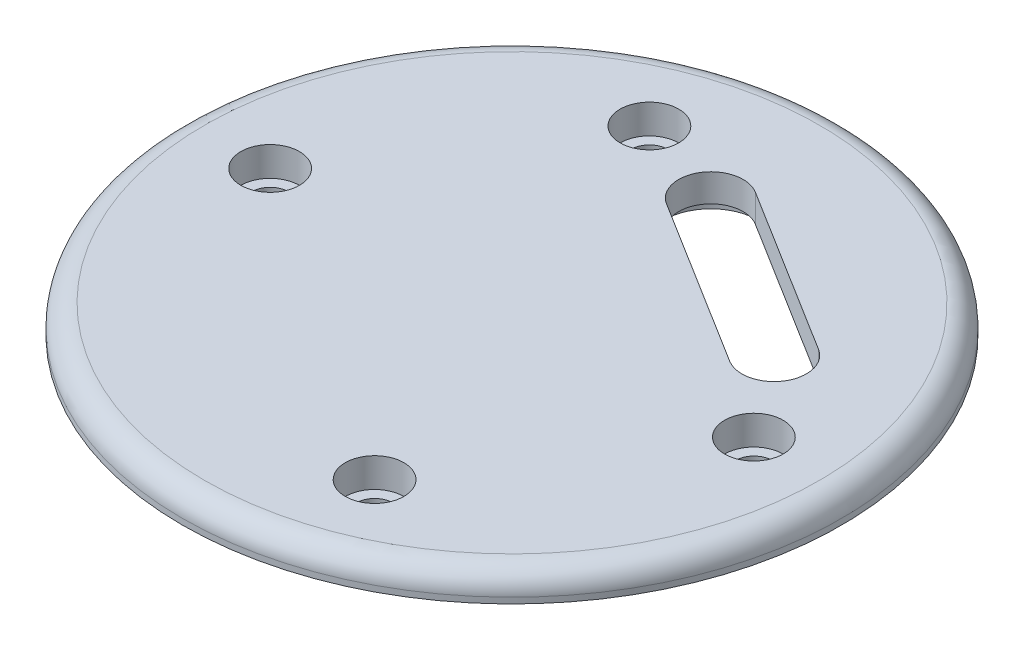
SolidWorks part; units mm, degrees
ref_plane "Front Plane" through (0, 0, 0) normal (0, 0, 1) x (1, 0, 0)
ref_plane "Top Plane" through (0, 0, 0) normal (0, 1, 0) x (1, 0, 0)
ref_plane "Right Plane" through (0, 0, 0) normal (1, 0, 0) x (0, 0, -1)
sketch "Sketch1" plane through (0, 0, 0) normal (0, 1, 0) x (1, 0, 0)
  circle A0 centre (0, 0) radius 22.5
  dimension "D1" = 45
extrude "Boss-Extrude1" add sketch "Sketch1" along normal blind 1.9
sketch "Sketch2" plane through (0, 0, 0) normal (0, -1, 0) x (1, 0, 0)
  circle A0 centre (16.1994, -0.3127) radius 1.25
  circle A1 centre (-5.762, -15.1432) radius 1.25
  circle A2 centre (-16.1994, 0.3127) radius 1.25
  circle A4 centre (5.762, 15.1432) radius 1.25
extrude "Cut-Extrude1" cut sketch "Sketch2" against normal through all
sketch "Sketch3" plane through (0, 1.9, 0) normal (0, 1, 0) x (1, 0, 0)
  line L3 (-0.4607, 11.287) -> (10.9956, 4.1452) construction
  line L6 (13.1116, 7.5397) -> (1.6554, 14.6814) construction
  line L7 (-0.4607, 11.287) -> (10.9956, 4.1452)
  line L8 (13.1116, 7.5397) -> (1.6554, 14.6814)
  line L9 (-0.5665, 11.1173) -> (10.8898, 3.9755)
  line L10 (13.2174, 7.7094) -> (1.7612, 14.8511)
  arc A6 (10.9956, 4.1452) -> (13.1116, 7.5397) centre (12.0536, 5.8425) ccw construction
  arc A7 (1.6554, 14.6814) -> (-0.4607, 11.287) centre (0.5974, 12.9842) ccw construction
  arc A8 (10.9956, 4.1452) -> (13.1116, 7.5397) centre (12.0536, 5.8425) ccw
  arc A9 (1.6554, 14.6814) -> (-0.4607, 11.287) centre (0.5974, 12.9842) ccw
  arc A10 (1.7612, 14.8511) -> (-0.5665, 11.1173) centre (0.5974, 12.9842) ccw
  arc A11 (10.8898, 3.9755) -> (13.2174, 7.7094) centre (12.0536, 5.8425) ccw
  dimension "D1" = 0.2
extrude "Cut-Extrude2" cut sketch "Sketch3" against normal blind 3 contours L8 A9 L7 A8 | L9 A11 L10 A10 A9 L8 A8 L7 region at (6.3255, 1.9, -9.4133) region at (-1.1032, 1.9, -14.0443)
sketch "Sketch5" plane through (0, 0, 0) normal (0, -1, 0) x (1, 0, 0)
  line L0 (-17.0875, 10.8507) -> (-17.5366, 13.064) construction
  line L1 (-17.5366, 13.064) -> (-5.5772, 21.1402) construction
  line L2 (-5.5772, 21.1402) -> (-3.6638, 19.8944) construction
  line L3 (-17.0875, 10.8507) -> (-17.5366, 13.064)
  line L4 (-17.5366, 13.064) -> (-5.5772, 21.1402)
  line L5 (-5.5772, 21.1402) -> (-3.6638, 19.8944)
  line L6 (-17.314, 12.973) -> (-5.5752, 20.9002)
  line L7 (-5.5752, 20.9002) -> (-3.7729, 19.7268)
  line L8 (-16.8915, 10.8904) -> (-17.314, 12.973)
  line L15 (13.2174, -7.7094) -> (1.7612, -14.8511) construction
  line L16 (-0.5665, -11.1173) -> (10.8898, -3.9755) construction
  line L17 (13.2174, -7.7094) -> (1.7612, -14.8511)
  line L18 (-0.5665, -11.1173) -> (10.8898, -3.9755)
  line L19 (-1.0955, -10.2687) -> (10.3607, -3.1269)
  line L20 (13.7465, -8.558) -> (2.2902, -15.6998)
  line L27 (24.6137, -13.9677) -> (22.4818, 0.9048)
  line L28 (24.6137, -13.9677) -> (22.4818, 0.9048)
  line L29 (22.1304, -15.5901) -> (24.6137, -13.9677)
  line L30 (22.1304, -15.5901) -> (24.6137, -13.9677)
  line L31 (19.3957, -11.4042) -> (22.1304, -15.5901)
  line L32 (19.3957, -11.4042) -> (22.1304, -15.5901)
  line L33 (5.387, -26.529) -> (2.6523, -22.3431)
  line L34 (5.387, -26.529) -> (2.6523, -22.3431)
  line L35 (2.9457, -28.124) -> (5.387, -26.529)
  line L36 (2.9457, -28.124) -> (5.387, -26.529)
  line L37 (-6.9155, -21.4109) -> (2.9457, -28.124)
  line L38 (-6.9155, -21.4109) -> (2.9457, -28.124)
  line L39 (-24.5718, 13.9951) -> (-22.3854, 2.2678)
  line L40 (-24.5718, 13.9951) -> (-22.3854, 2.2678)
  line L41 (-22.1304, 15.5901) -> (-24.5718, 13.9951)
  line L42 (-22.1304, 15.5901) -> (-24.5718, 13.9951)
  line L43 (-19.3957, 11.4042) -> (-22.1304, 15.5901)
  line L44 (-19.3957, 11.4042) -> (-22.1304, 15.5901)
  line L45 (-5.387, 26.529) -> (-2.6523, 22.3431)
  line L46 (-5.387, 26.529) -> (-2.6523, 22.3431)
  line L47 (-2.9037, 28.1514) -> (-5.387, 26.529)
  line L48 (-2.9037, 28.1514) -> (-5.387, 26.529)
  line L49 (9.8596, 20.2247) -> (-2.9037, 28.1514)
  line L50 (9.8596, 20.2247) -> (-2.9037, 28.1514)
  arc A0 (-17.3572, 8.8869) -> (-17.0875, 10.8507) centre (-20.0276, 10.2541) ccw construction
  arc A1 (2.6523, -22.3431) -> (19.3957, -11.4042) centre (0, 0) ccw
  arc A3 (-17.3572, 8.8869) -> (-1.7567, 19.4207) centre (0, 0) ccw construction
  arc A4 (-3.6638, 19.8944) -> (-1.7567, 19.4207) centre (-2.0269, 22.4085) ccw construction
  arc A5 (-17.3572, 8.8869) -> (-17.0875, 10.8507) centre (-20.0276, 10.2541) ccw
  arc A6 (-17.3572, 8.8869) -> (-1.7567, 19.4207) centre (0, 0) ccw
  arc A7 (-3.6638, 19.8944) -> (-1.7567, 19.4207) centre (-2.0269, 22.4085) ccw
  arc A8 (-3.7729, 19.7268) -> (-1.7387, 19.2215) centre (-2.0269, 22.4085) ccw
  arc A9 (-17.1792, 8.7958) -> (-1.7387, 19.2215) centre (0, 0) ccw
  arc A10 (-17.1792, 8.7958) -> (-16.8915, 10.8904) centre (-20.0276, 10.2541) ccw
  circle A11 centre (-16.1994, 0.3127) radius 2
  circle A12 centre (5.762, 15.1432) radius 2
  circle A13 centre (16.1994, -0.3127) radius 2
  circle A14 centre (-5.762, -15.1432) radius 2
  arc A21 (-0.5665, -11.1173) -> (1.7612, -14.8511) centre (0.5974, -12.9842) ccw construction
  arc A22 (13.2174, -7.7094) -> (10.8898, -3.9755) centre (12.0536, -5.8425) ccw construction
  arc A23 (-0.5665, -11.1173) -> (1.7612, -14.8511) centre (0.5974, -12.9842) ccw
  arc A24 (13.2174, -7.7094) -> (10.8898, -3.9755) centre (12.0536, -5.8425) ccw
  arc A25 (2.6523, -22.3431) -> (19.3957, -11.4042) centre (0, 0) ccw
  arc A26 (-22.3854, 2.2678) -> (-6.9155, -21.4109) centre (0, 0) ccw
  arc A27 (-22.3854, 2.2678) -> (-6.9155, -21.4109) centre (0, 0) ccw
  arc A28 (-2.6523, 22.3431) -> (-19.3957, 11.4042) centre (0, 0) ccw
  arc A29 (-2.6523, 22.3431) -> (-19.3957, 11.4042) centre (0, 0) ccw
  arc A30 (22.4818, 0.9048) -> (9.8596, 20.2247) centre (0, 0) ccw
  arc A31 (22.4818, 0.9048) -> (9.8596, 20.2247) centre (0, 0) ccw
  arc A32 (13.7465, -8.558) -> (10.3607, -3.1269) centre (12.0536, -5.8425) ccw
  arc A33 (-1.0955, -10.2687) -> (2.2902, -15.6998) centre (0.5974, -12.9842) ccw
  dimension "D3" = 1
  dimension "D4" = 18.65
  dimension "D8" = 4
  dimension "D5" = 26.5
  dimension "D6" = 18.65
  dimension "D7" = 15.1432
  dimension "D1" = 0
  dimension "D2" = 0.2
extrude "Boss-Extrude2" add sketch "Sketch5" along normal blind 1 contours A10 A9 A8 L7 L6 L8 A33 L19 A32 L20 A14 A13 A12 A11 region at (-1.0043, 0, 1.4925)
sketch "Sketch6" plane through (0, 1.9, 0) normal (0, 1, 0) x (1, 0, 0)
  circle A0 centre (-16.1994, -0.3127) radius 2
  circle A1 centre (-5.762, 15.1432) radius 2
  circle A2 centre (5.762, -15.1432) radius 2
  circle A3 centre (16.1994, 0.3127) radius 2
extrude "Cut-Extrude3" cut sketch "Sketch6" against normal blind 2
fillet "Fillet2" radius 1.5 1 edges at (0, 1.9, 22.5)
sketch "Sketch7" plane through (0, -1, 0) normal (0, -1, 0) x (1, 0, 0)
  circle A0 centre (5.762, 15.1432) radius 1.25
  circle A1 centre (16.1994, -0.3127) radius 1.25
  circle A2 centre (-16.1994, 0.3127) radius 1.25
  circle A3 centre (-5.762, -15.1432) radius 1.25
  circle A4 centre (-16.1994, 0.3127) radius 2.5
  circle A5 centre (5.762, 15.1432) radius 2.5
  circle A6 centre (16.1994, -0.3127) radius 2.5
  circle A7 centre (-5.762, -15.1432) radius 2.5
  dimension "D1" = 1.25
  dimension "D2" = 1.25
  dimension "D3" = 1.25
  dimension "D4" = 1.25
extrude "Boss-Extrude3" add sketch "Sketch7" along normal blind 1.1
chamfer "Chamfer2" distance 0.55 angle 45 8 edges at (-16.1994, -2.1, -2.1873) (-16.1994, -1, -2.1873) (16.1994, -1, -2.8127) (5.762, -1, 12.6432) (16.1994, -2.1, -2.8127) (5.762, -2.1, 12.6432) (-5.762, -2.1, -17.6432) (-5.762, -1, -17.6432)
sketch "Sketch10" plane through (0, -1, 0) normal (0, 1, 0) x (1, 0, 0)
  circle A0 centre (-5.762, 15.1432) radius 2
  circle A1 centre (-5.762, 15.1432) radius 1.25
  circle A2 centre (5.762, -15.1432) radius 2 construction
  circle A3 centre (16.1994, 0.3127) radius 2 construction
  circle A4 centre (-16.1994, -0.3127) radius 2 construction
  circle A5 centre (5.762, -15.1432) radius 2
  circle A6 centre (16.1994, 0.3127) radius 2
  circle A7 centre (-16.1994, -0.3127) radius 2
  circle A8 centre (16.1994, 0.3127) radius 1.25 construction
  circle A9 centre (-16.1994, -0.3127) radius 1.25 construction
  circle A10 centre (5.762, -15.1432) radius 1.25 construction
  circle A11 centre (16.1994, 0.3127) radius 1.25
  circle A12 centre (-16.1994, -0.3127) radius 1.25
  circle A13 centre (5.762, -15.1432) radius 1.25
extrude "Boss-Extrude4" add sketch "Sketch10" along normal blind 0.9
